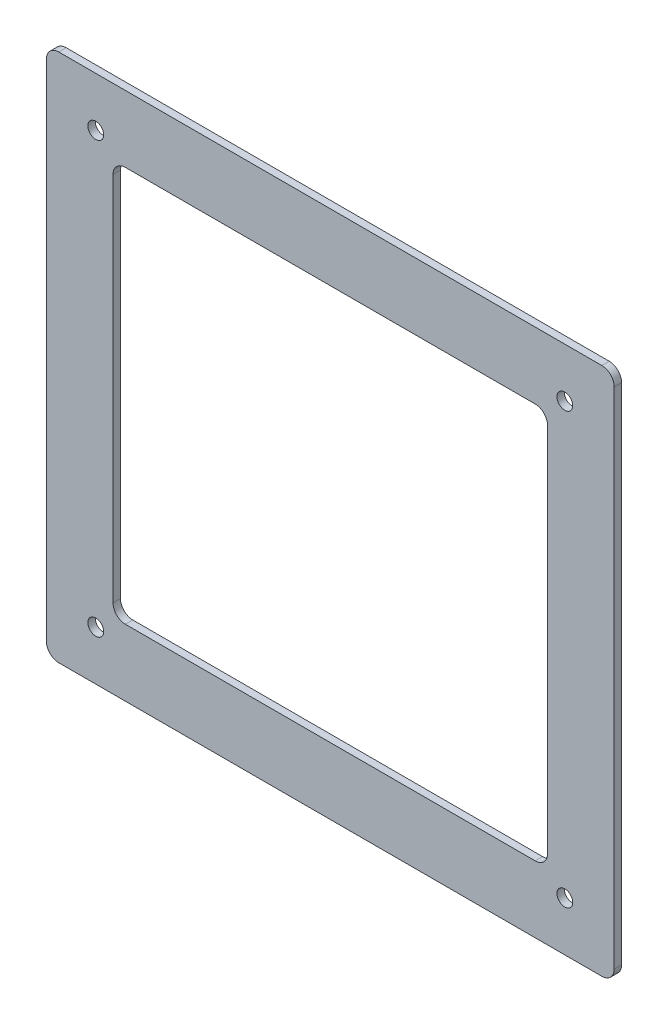
SolidWorks part; units mm, degrees
ref_plane "前视基准面" through (0, 0, 0) normal (0, 0, 1) x (1, 0, 0)
ref_plane "上视基准面" through (0, 0, 0) normal (0, 1, 0) x (1, 0, 0)
ref_plane "右视基准面" through (0, 0, 0) normal (1, 0, 0) x (0, 0, -1)
sketch "草图1" plane through (0, 0, 0) normal (0, 0, 1) x (1, 0, 0)
  line L1 (88, -80.125) -> (-88, -80.125)
  line L2 (88, -80.125) -> (88, 80.125)
  line L3 (88, 80.125) -> (-88, 80.125)
  line L4 (-88, -80.125) -> (-88, 80.125)
  line L5 (88, -80.125) -> (-88, 80.125) construction
  line L6 (88, 80.125) -> (-88, -80.125) construction
  line L7 (115, -107.125) -> (-115, -107.125)
  line L8 (115, -107.125) -> (115, 107.125)
  line L9 (115, 107.125) -> (-115, 107.125)
  line L10 (-115, -107.125) -> (-115, 107.125)
  line L11 (115, -107.125) -> (-115, 107.125) construction
  line L12 (115, 107.125) -> (-115, -107.125) construction
  point P0 (0, 0)
  point P6 (0, 0)
  dimension "D1" = 27
  dimension "D2" = 27
  dimension "D3" = 160.25
  dimension "D4" = 176
extrude "凸台-拉伸1" add sketch "草图1" along normal blind 3
fillet "圆角1" radius 5 8 edges at (88, -80.125, 1.5) (-115, 107.125, 1.5) (-88, 80.125, 1.5) (115, -107.125, 1.5) (-115, -107.125, 1.5) (88, 80.125, 1.5) (115, 107.125, 1.5) (-88, -80.125, 1.5)
sketch "草图2" plane through (0, 0, 3) normal (0, 0, 1) x (1, 0, 0)
  line L0 (83, 80.125) -> (-83, 80.125) construction
  line L1 (-88, 75.125) -> (-88, -75.125) construction
  line L2 (88, -75.125) -> (88, 75.125) construction
  line L3 (-83, -80.125) -> (83, -80.125) construction
  point P0 (-95, 87.125)
  point P1 (-95, -87.125)
  point P2 (95, -87.125)
  point P3 (95, 87.125)
  dimension "D1" = 7
  dimension "D2" = 7
  dimension "D3" = 7
  dimension "D4" = 7
  dimension "D5" = 7
  dimension "D6" = 7
  dimension "D7" = 7
  dimension "D8" = 7
hole_wizard "Ø6.4 (6.4) 直径孔1" positions "草图3" profile "草图4" hole size "Ø6.4" standard "GB" end condition up to next
sketch "草图3" plane through (0, 0, 3) normal (0, 0, 1) x (1, 0, 0)
  point P0 (-95, 87.125)
  point P3 (95, 87.125)
  point P6 (95, -87.125)
  point P9 (-95, -87.125)
sketch "草图4" plane through (-95, 87.125, 3) normal (1, 0, 0) x (0, -1, 0)
  line L0 (0, 0) -> (0, 3)
  line L1 (0, 3) -> (3.2, 3)
  line L2 (3.2, 3) -> (3.2, 0)
  line L5 (3.2, 0) -> (0, 0)
  line L11 (0, -6.35) -> (0, 107.95) construction
  dimension "通孔孔直径" = 6.4
  dimension "通孔孔深度" = 3
